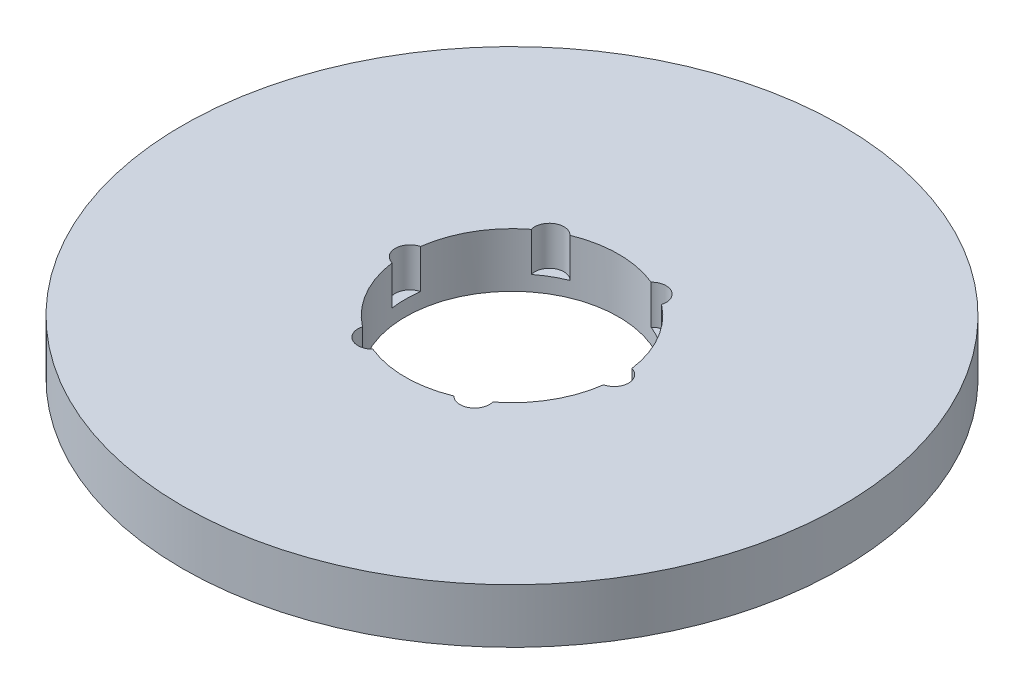
SolidWorks part; units mm, degrees
ref_plane "Front Plane" through (0, 0, 0) normal (0, 0, 1) x (1, 0, 0)
ref_plane "Top Plane" through (0, 0, 0) normal (0, 1, 0) x (1, 0, 0)
ref_plane "Right Plane" through (0, 0, 0) normal (1, 0, 0) x (0, 0, -1)
sketch "Sketch1" plane through (0, 0, 0) normal (0, 1, 0) x (1, 0, 0)
  circle A0 centre (0, 0) radius 85
  dimension "FLANGE_OD" = 170
extrude "Boss-Extrude1" add sketch "Sketch1" along normal blind 14
sketch "Sketch2" plane through (0, 0, 0) normal (0, 1, 0) x (1, 0, 0)
  circle A0 centre (0, 0) radius 27.5
  dimension "BORE_D" = 55
extrude "Cut-Extrude1" cut sketch "Sketch2" along normal through all
sketch "Sketch3" plane through (0, 14, 0) normal (0, 1, 0) x (1, 0, 0)
  circle A0 centre (0, 0) radius 26.3248 construction
  circle A1 centre (-26.3248, 0) radius 3.7718
  dimension "BOLT_D" = 7.5436
  dimension "BOLT_PCD" = 52.6496
extrude "Cut-Extrude2" cut sketch "Sketch3" against normal blind 10.0717
pattern_circular "CirPattern1" count 6 over 360 about axis through (0, 0, 0) along (0, 1, 0) of "Cut-Extrude2"
